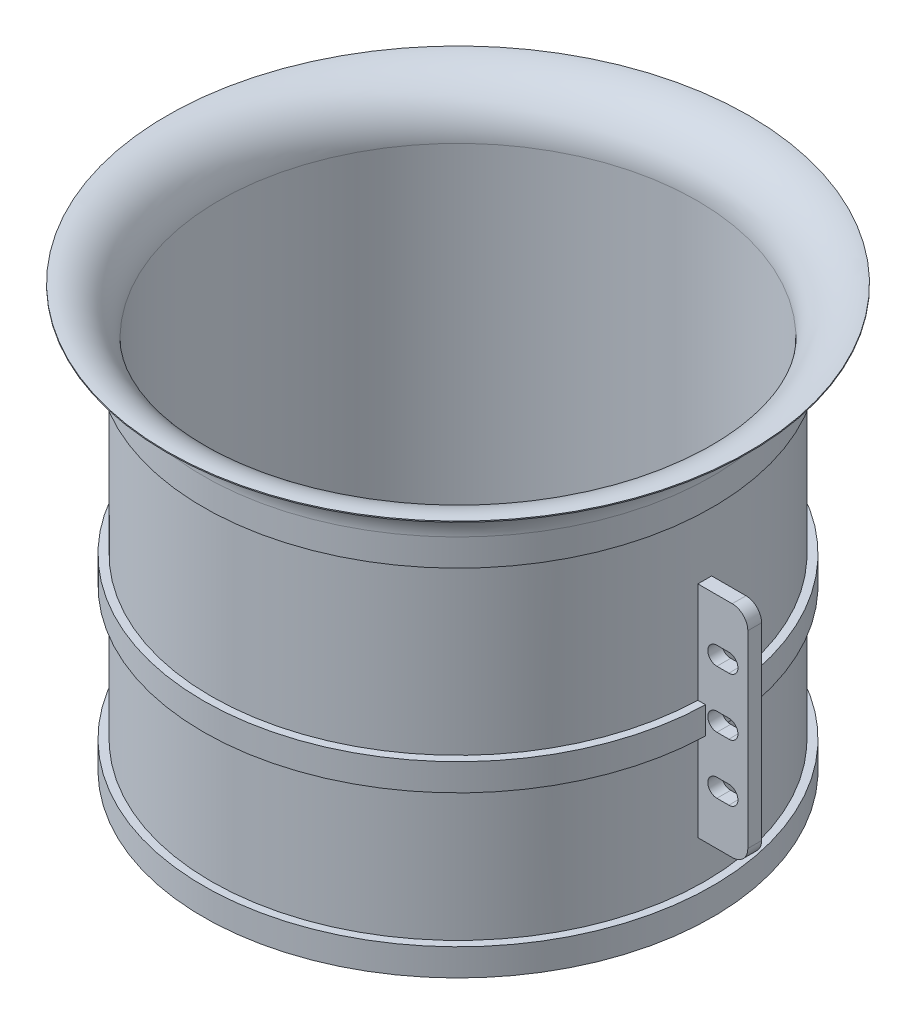
SolidWorks part; units mm, degrees
ref_plane "Front Plane" through (0, 0, 0) normal (0, 0, 1) x (1, 0, 0)
ref_plane "Top Plane" through (0, 0, 0) normal (0, 1, 0) x (1, 0, 0)
ref_plane "Right Plane" through (0, 0, 0) normal (1, 0, 0) x (0, 0, -1)
sketch "Sketch2" plane through (0, 0, 0) normal (0, 0, 1) x (1, 0, 0)
  line L0 (46, 0) -> (46, 71.9367)
  line L1 (46, 0) -> (49, 0)
  line L2 (49, 0) -> (49, 5.2)
  line L3 (49, 5.2) -> (47.5, 5.2)
  line L4 (47.5, 5.2) -> (47.5, 30.85)
  line L5 (47.5, 30.85) -> (49, 30.85)
  line L6 (49, 30.85) -> (49, 36.05)
  line L7 (49, 36.05) -> (47.5, 36.05)
  line L8 (47.5, 36.05) -> (47.5, 68.3)
  line L9 (47.5, 68.3) -> (49, 68.3)
  line L10 (49, 68.3) -> (49, 73.5)
  line L11 (56, 80.9) -> (56, 81.1)
  line L12 (56, 81.1) -> (56.5989, 81.0476) construction
  line L13 (0, 0) -> (0, 71.1009) construction
  arc A1 (46, 71.9367) -> (56, 81.1) centre (55.1983, 71.9367) cw
  arc A2 (49, 73.5) -> (56, 80.9) centre (56.4114, 73.5) cw
  dimension "D2" = 49
  dimension "D3" = 1.5
  dimension "D4" = 5.2
  dimension "D5" = 36.05
  dimension "D6" = 81.1
  dimension "D7" = 73.5
  dimension "D8" = 0.2
  dimension "D9" = 56
  dimension "D10" = 85
  dimension "D11" = 3
revolve "Revolve1" add sketch "Sketch2" angle 360 about L13
sketch "Sketch3" plane through (0, 0, 0) normal (0, 0, 1) x (1, 0, 0)
  line L0 (47.5, 55.45) -> (57.1, 55.45)
  line L1 (47.5, 36.05) -> (47.5, 68.3) construction
  line L2 (57.1, 55.45) -> (57.1, 13.15)
  line L3 (57.1, 13.15) -> (47.5, 13.15)
  line L4 (47.5, 5.2) -> (47.5, 30.85) construction
  line L5 (51.15, 34.3) -> (53.45, 34.3) construction
  line L6 (51.15, 36.05) -> (53.45, 36.05)
  line L7 (51.15, 32.55) -> (53.45, 32.55)
  line L8 (52.3, 34.3) -> (52.3, 13.15) construction
  line L9 (51.15, 23.3) -> (53.45, 23.3) construction
  line L10 (51.15, 25.05) -> (53.45, 25.05)
  line L11 (51.15, 21.55) -> (53.45, 21.55)
  line L12 (52.3, 34.3) -> (57.1, 34.3) construction
  line L13 (51.15, 45.3) -> (53.45, 45.3) construction
  line L14 (51.15, 43.55) -> (53.45, 43.55)
  line L15 (51.15, 47.05) -> (53.45, 47.05)
  line L16 (47.5, 36.05) -> (47.5, 68.3) construction
  line L17 (47.5, 36.05) -> (47.5, 68.3)
  line L19 (49, 36.05) -> (47.5, 36.05) construction
  line L20 (49, 36.05) -> (47.5, 36.05)
  line L21 (47.5, 30.85) -> (49, 30.85) construction
  line L22 (49, 30.85) -> (49, 36.05) construction
  line L23 (47.5, 5.2) -> (47.5, 30.85) construction
  line L24 (49, 30.85) -> (49, 36.05)
  line L25 (47.5, 5.2) -> (47.5, 30.85)
  line L27 (47.5, 30.85) -> (49, 30.85)
  line L28 (47.5, 55.45) -> (46, 55.45)
  line L29 (46, 55.45) -> (46, 13.15)
  line L30 (46, 13.15) -> (47.5, 13.15)
  line L31 (46, 0) -> (46, 71.9367) construction
  arc A0 (51.15, 36.05) -> (51.15, 32.55) centre (51.15, 34.3) ccw
  arc A1 (53.45, 32.55) -> (53.45, 36.05) centre (53.45, 34.3) ccw
  arc A2 (51.15, 25.05) -> (51.15, 21.55) centre (51.15, 23.3) ccw
  arc A3 (53.45, 21.55) -> (53.45, 25.05) centre (53.45, 23.3) ccw
  arc A4 (51.15, 43.55) -> (51.15, 47.05) centre (51.15, 45.3) cw
  arc A5 (53.45, 47.05) -> (53.45, 43.55) centre (53.45, 45.3) cw
  point P4 (57.1, 34.3)
  point P12 (52.3, 34.3)
  point P23 (52.3, 23.3)
  point P29 (52.3, 45.3)
  dimension "D5" = 2.3
  dimension "D1" = 42.3
  dimension "D2" = 57.1
  dimension "D3" = 34.3
  dimension "D4" = 3.5
  dimension "D7" = 11
  dimension "D6" = 2
extrude "Boss-Extrude1" add sketch "Sketch3" along normal blind 1.325 and the other way blind 1.325 contours L11 A3 L10 A2 | L7 A1 L6 A0 | A5 L15 A4 L14 | L2 L3 L30 L29 L28 L0 region at (52.3, 34.3, 0) region at (52.3, 23.3, 0) region at (52.3, 45.3, 0)
fillet "Fillet1" radius 3 2 edges at (57.1, 13.15, 0) (57.1, 55.45, 0)
mirror "Mirror1" about plane through (0, 0, 0) normal (1, 0, 0) of "Boss-Extrude1", "Fillet1"
